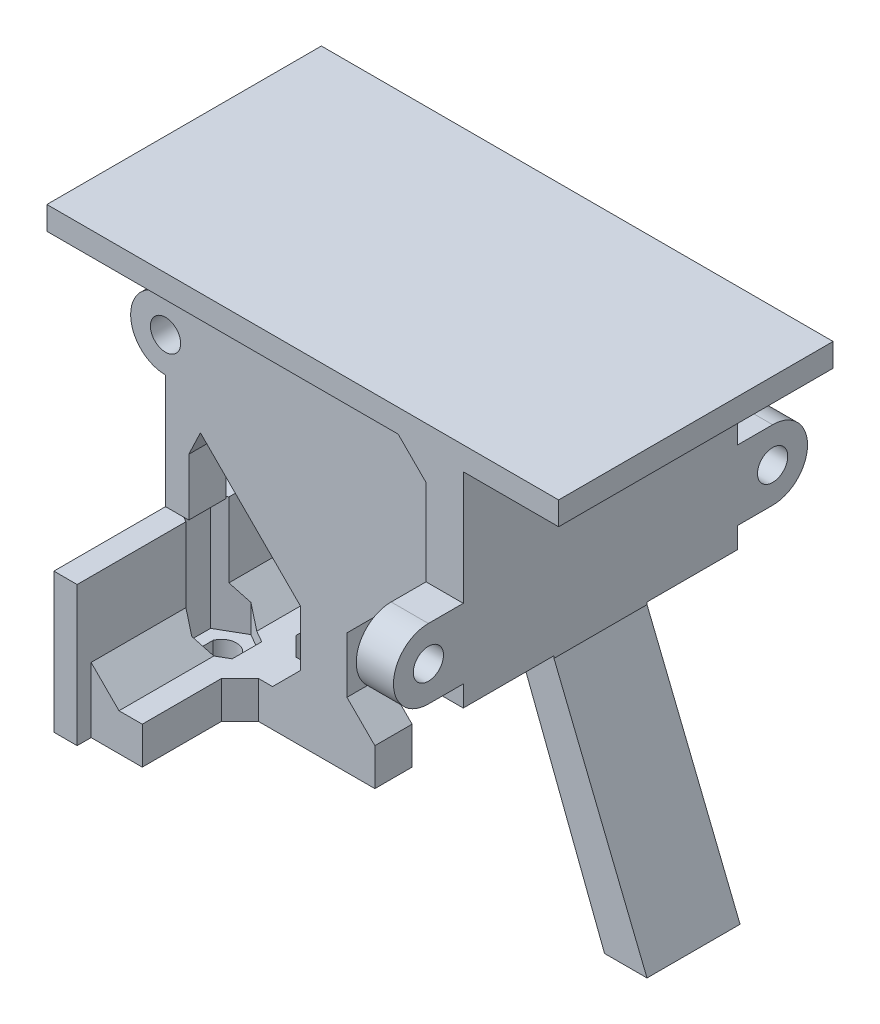
SolidWorks part; units mm, degrees
ref_plane "Alzado" through (0, 0, 0) normal (0, 0, 1) x (1, 0, 0)
ref_plane "Planta" through (0, 0, 0) normal (0, 1, 0) x (1, 0, 0)
ref_plane "Vista lateral" through (0, 0, 0) normal (1, 0, 0) x (0, 0, -1)
sketch "Croquis1" plane through (0, 0, 0) normal (0, 0, 1) x (1, 0, 0)
  line L0 (-14.75, 6) -> (-14.75, 3.75)
  line L1 (-14.75, 6) -> (14.75, 6)
  line L3 (-14.75, -6) -> (14.75, -6)
  line L5 (-14.75, 4.0227) -> (22, -6) construction
  line L6 (-22, -6) -> (22, 6) construction
  line L7 (-14.75, 3.75) -> (-18.5, 3.75)
  line L8 (-18.5, -3.75) -> (-14.75, -3.75)
  line L9 (-14.75, -3.75) -> (-14.75, -6)
  line L10 (14.75, -6) -> (14.75, -3.75)
  line L11 (14.75, -3.75) -> (18.5, -3.75)
  line L12 (14.75, 6) -> (14.75, 3.75)
  line L13 (14.75, 3.75) -> (18.5, 3.75)
  circle A0 centre (-18.5, 0) radius 1.625
  circle A1 centre (18.5, 0) radius 1.625
  arc A2 (-18.5, 3.75) -> (-18.5, -3.75) centre (-18.5, 0) ccw
  arc A3 (18.5, -3.75) -> (18.5, 3.75) centre (18.5, 0) ccw
  point P0 (0, 0)
  dimension "D1" = 3.25
  dimension "D6" = 7.5
  dimension "D7" = 7.5
  dimension "D2" = 37
  dimension "D3" = 18.5
  dimension "D5" = 12
extrude "Saliente-Extruir1" add sketch "Croquis1" along normal blind 4
sketch "Croquis2" plane through (0, 0, 4) normal (0, 0, 1) x (1, 0, 0)
  line L0 (-14.75, -6) -> (14.75, -6) construction
  line L1 (-4, -6) -> (1, -6)
  line L2 (-4, -6) -> (-4, -31)
  line L3 (-4, -31) -> (1, -31)
  line L4 (1, -6) -> (1, -31)
  dimension "D1" = 5
  dimension "D2" = 4
  dimension "D3" = 25
extrude "Saliente-Extruir2" add sketch "Croquis2" against normal blind 4
sketch "Croquis3" plane through (0, -31, 0) normal (0, -1, 0) x (1, 0, 0)
  line L0 (-10.5, -1.5) -> (-10.5, -10.5)
  line L5 (-18.5, 14.5) -> (-10.5, 14.5)
  line L6 (-18.5, 14.5) -> (-18.5, -10.5)
  line L7 (-22.25, 2) -> (-12.4182, 2) construction
  line L13 (-18.5, -10.5) -> (-10.5, -10.5)
  line L15 (-10.5, 14.5) -> (-10.5, 5.5)
  line L16 (-10.5, 5.5) -> (4, 5.5)
  line L19 (-10.5, -1.5) -> (4, -1.5)
  line L20 (4, 5.5) -> (4, -1.5)
  line L21 (-18.5, 4) -> (-18.5, 0) construction
  circle A4 centre (-14.5, 2) radius 1.625
  line M6 (1, 4) -> (-4, 4)
  line M7 (-4, 4) -> (-4, 0)
  line M8 (-4, 0) -> (1, 0)
  line M9 (1, 0) -> (1, 4)
  dimension "D3" = 25
  dimension "D9" = 7
  dimension "D5" = 3.25
  dimension "D10" = 4
  dimension "D1" = 8
  dimension "D2" = 12.5
  dimension "D8" = 3.5
  dimension "D6" = 12.5
extrude "Saliente-Extruir3" add sketch "Croquis3" against normal blind 4 contours M8 | M9 M6 M7 M8 | M7 M6 M9 region at (-11.2721, -31, 2) region at (-1.5, -31, 2)
chamfer "Chaflán1" distance 3 angle 45 1 edges at (-4, -27, 2)
chamfer "Chaflán2" distance 1.5 angle 45 2 edges at (-10.5, -29, -1.5) (-10.5, -29, 5.5)
sketch "Croquis4" plane through (0, 0, 4) normal (0, 0, 1) x (1, 0, 0)
  line L1 (18.5, -6) -> (26.25, -6)
  line L2 (18.5, -6) -> (18.5, 6)
  line L3 (18.5, 6) -> (26.25, 6)
  line L4 (26.25, -6) -> (26.25, 6)
  arc A0 (18.5, -3.75) -> (18.5, 3.75) centre (18.5, 0) ccw construction
  circle A1 centre (18.5, 0) radius 1.625 construction
  point P7 (22.25, 0)
  dimension "D1" = 4
  dimension "D2" = 0
extrude "Saliente-Extruir4" add sketch "Croquis4" along normal blind 21 and the other way blind 25
sketch "Croquis5" plane through (0, 6, 0) normal (0, 1, 0) x (1, 0, 0)
  line L0 (26.25, 21) -> (18.5, 21) construction
  line L1 (18.5, 0) -> (22.25, 0)
  line L2 (18.5, 0) -> (18.5, 21)
  line L3 (18.5, 21) -> (22.25, 21)
  line L4 (22.25, 0) -> (22.25, 21)
  line L6 (18.5, -4) -> (22.25, -4)
  line L7 (18.5, -4) -> (18.5, -25)
  line L8 (18.5, -25) -> (22.25, -25)
  line L9 (22.25, -4) -> (22.25, -25)
  line L10 (26.25, -25) -> (18.5, -25) construction
  line L11 (26.25, 21) -> (26.25, -25) construction
  line L12 (14.75, -4) -> (-14.75, -4) construction
  dimension "D1" = 4
  dimension "D2" = 4
extrude "Cortar-Extruir1" cut sketch "Croquis5" against normal through all both and the other way through all
sketch "Croquis6" plane through (0, 0, 4) normal (0, 0, 1) x (1, 0, 0)
  line L0 (18.5, -1.625) -> (18.5, 1.625) construction
  line L1 (18.5, 3.75) -> (22.25, 6)
  line L2 (22.25, 6) -> (18.5, 6)
  line L3 (18.5, 6) -> (18.5, 3.75)
  line L4 (18.5, -3.75) -> (22.25, -6)
  line L5 (22.25, -6) -> (18.5, -6)
  line L6 (18.5, -6) -> (18.5, -3.75)
  circle A0 centre (18.5, 0) radius 1.625
extrude "Cortar-Extruir2" cut sketch "Croquis6" against normal through all both and the other way through all
chamfer "Chaflán4" distance 5 angle 45 2 edges at (22.25, 0, 0) (22.25, 0, 4)
sketch "Croquis7" plane through (0, 0, 4) normal (0, 0, 1) x (1, 0, 0)
  circle A0 centre (18.5, 0) radius 3.745
  dimension "D1" = 7.49
extrude "Cortar-Extruir5" cut sketch "Croquis7" along normal blind 22
sketch "Croquis8" plane through (0, 0, 0) normal (0, 0, -1) x (-1, 0, 0)
  circle A0 centre (-18.5, 0) radius 3.745
extrude "Cortar-Extruir6" cut sketch "Croquis8" along normal blind 22
sketch "Croquis9" plane through (26.25, 0, 0) normal (1, 0, 0) x (0, 0, -1)
  line L1 (-16.75, 6) -> (-16.75, 3.75)
  line L2 (21, 6) -> (-25, 6) construction
  line L3 (-16.75, 3.75) -> (-20.5, 3.75)
  line L4 (-16.75, -6) -> (-16.75, -3.75)
  line L5 (21, -6) -> (-25, -6) construction
  line L6 (-16.75, -3.75) -> (-20.5, -3.75)
  line L7 (12.75, -6) -> (12.75, -3.75)
  line L8 (12.75, -3.75) -> (16.5, -3.75)
  line L9 (12.75, 6) -> (12.75, 3.75)
  line L10 (12.75, 3.75) -> (16.5, 3.75)
  line L11 (-16.75, 6) -> (-25, 6)
  line L12 (-25, 6) -> (-25, -6)
  line L13 (-25, -6) -> (-16.75, -6)
  line L14 (12.75, 6) -> (21, 6)
  line L15 (21, -6) -> (21, 6) construction
  line L16 (21, 6) -> (21, -6)
  line L17 (21, -6) -> (12.75, -6)
  line L18 (-2, 1.625) -> (-2, 19.0588) construction
  line L19 (0, 1.625) -> (-4, 1.625) construction
  arc A2 (-20.5, 3.75) -> (-20.5, -3.75) centre (-20.5, 0) ccw
  arc A3 (16.5, -3.75) -> (16.5, 3.75) centre (16.5, 0) ccw
  dimension "D1" = 37
  dimension "D2" = 18.5
  dimension "D4" = 7.5
extrude "Cortar-Extruir7" cut sketch "Croquis9" against normal blind 22
sketch "Croquis10" plane through (26.25, 0, 0) normal (1, 0, 0) x (0, 0, -1)
  line L0 (-2, -1.625) -> (-2, 16.9497) construction
  circle A0 centre (-20.5, 0) radius 1.625
  circle A1 centre (16.5, 0) radius 1.625
  arc A2 (-20.5, 3.75) -> (-20.5, -3.75) centre (-20.5, 0) ccw construction
  arc A3 (16.5, -3.75) -> (16.5, 3.75) centre (16.5, 0) ccw construction
  dimension "D1" = 3.25
  dimension "D2" = 3.25
extrude "Cortar-Extruir8" cut sketch "Croquis10" against normal blind 22
chamfer "Chaflán5" distance 12 angle 45 2 edges at (-4, -6, 2) (1, -6, 2)
sketch "Croquis11" plane through (0, -31, 0) normal (0, -1, 0) x (1, 0, 0)
  line L0 (4, 2) -> (-9.3695, 2) construction
  line L1 (-18.5, 16) -> (-16, 16)
  line L2 (-18.5, 16) -> (-18.5, -12)
  line L3 (-18.5, -12) -> (-16, -12)
  line L4 (-16, 16) -> (-16, -12)
  line L5 (-18.5, 14.5) -> (-18.5, -10.5) construction
  dimension "D1" = 28
  dimension "D2" = 14
  dimension "D3" = 2.5
extrude "Saliente-Extruir5" add sketch "Croquis11" against normal blind 15
chamfer "Chaflán6" distance 3 angle 45 2 edges at (-16, -27, -4.5625) (-16, -27, 8.5625)
sketch "Croquis12" plane through (0, -31, 0) normal (0, -1, 0) x (1, 0, 0)
  line L13 (-11.75, 0.4123) -> (-11.75, 3.5877)
  line L14 (-11.75, 3.5877) -> (-14.5, 5.1754)
  line L15 (-14.5, 5.1754) -> (-17.25, 3.5877)
  line L16 (-17.25, 3.5877) -> (-17.25, 0.4123)
  line L17 (-17.25, 0.4123) -> (-14.5, -1.1754)
  line L18 (-14.5, -1.1754) -> (-11.75, 0.4123)
  circle A0 centre (-14.5, 2) radius 2.75 construction
  dimension "D1" = 5.5
extrude "Cortar-Extruir9" cut sketch "Croquis12" against normal up to surface (15 mm away) from offset 2.5 up to face at (-17.25, -16, 2) offset against normal yes
sketch "Croquis13" plane through (0, -27, 0) normal (0, 1, 0) x (1, 0, 0)
  line L0 (-10.5, 3) -> (-10.5, 2)
  line L1 (-10.5, 2) -> (-8.5, 0)
  line L2 (14.75, 0) -> (-14.75, 0) construction
  line L3 (-8.5, 0) -> (4, 0)
  line L4 (4, 0) -> (4, 5.165)
  line L5 (4, 5.165) -> (-10.5, 3)
  line L6 (-18.5, -2) -> (0.9317, -2) construction
  line L7 (-18.5, -4) -> (-18.5, 0) construction
  line L8 (4, -9.165) -> (-10.5, -7)
  line L9 (4, -4) -> (4, -9.165)
  line L10 (-8.5, -4) -> (4, -4)
  line L11 (-10.5, -6) -> (-8.5, -4)
  line L12 (-10.5, -7) -> (-10.5, -6)
  dimension "D1" = 2
  dimension "D2" = 2
extrude "Cortar-Extruir10" cut sketch "Croquis13" against normal blind 10
sketch "Croquis14" plane through (26.25, 0, 0) normal (1, 0, 0) x (0, 0, -1)
  line L0 (2, -31) -> (10.5, -31) construction
  line L1 (-7, -6) -> (3, -6)
  line L2 (-7, -6) -> (-7, -31)
  line L3 (-7, -31) -> (3, -31)
  line L4 (3, -6) -> (3, -31)
  line L5 (-4, -27) -> (-4, -18) construction
  dimension "D1" = 10
  dimension "D2" = 3
  dimension "D3" = 25
extrude "Saliente-Extruir6" add sketch "Croquis14" against normal blind 8 and the other way blind 10
sketch "Croquis15" plane through (0, 6, 0) normal (0, 1, 0) x (1, 0, 0)
  line L0 (14.75, -4) -> (14.75, 0) construction
  line L1 (-14.75, -4) -> (14.75, -4)
  line L2 (-14.75, -4) -> (-14.75, 0)
  line L3 (-14.75, 0) -> (14.75, 0)
  line L4 (14.75, -4) -> (14.75, 0)
  line L6 (22.25, 12.75) -> (26.25, 12.75)
  line L7 (22.25, 12.75) -> (22.25, -16.75)
  line L8 (22.25, -16.75) -> (26.25, -16.75)
  line L9 (26.25, 12.75) -> (26.25, -16.75)
extrude "Saliente-Extruir7" add sketch "Croquis15" along normal blind 10
sketch "Croquis16" plane through (0, 16, 0) normal (0, 1, 0) x (1, 0, 0)
  line L1 (-18.5, 12.75) -> (36.5, 12.75)
  line L2 (-18.5, 12.75) -> (-18.5, -16.75)
  line L3 (-18.5, -16.75) -> (36.5, -16.75)
  line L4 (36.5, 12.75) -> (36.5, -16.75)
  line L6 (26.25, 12.75) -> (22.25, 12.75) construction
  line L7 (-18.5, -16) -> (-18.5, 12) construction
  dimension "D1" = 29.5
  dimension "D2" = 55
extrude "Saliente-Extruir8" add sketch "Croquis16" along normal blind 2.5
chamfer "Chaflán7" distance 3 angle 45 3 edges at (14.75, 16, 2) (-14.75, 16, 2) (22.25, 16, 2)
sketch "Croquis17" plane through (0, 0, 4) normal (0, 0, 1) x (1, 0, 0)
  line L0 (-18.5, -16) -> (-18.5, -3.75)
  line L1 (-18.5, -3.75) -> (-14.75, -3.75)
  line L2 (-14.75, -3.75) -> (-14.75, -7.25)
  line L3 (-14.75, -7.25) -> (-16, -9.875)
  line L4 (-16, -9.875) -> (-16, -16)
  line L5 (-16, -16) -> (-18.5, -16)
extrude "Saliente-Extruir9" add sketch "Croquis17" against normal up to surface (4 mm away) up to face at (0.9325, -7.3558, 0)
chamfer "Chaflán11" distance 3 1 edges at (1, -27, 2)
chamfer "Chaflán12" distance 25 angle 22 1 edges at (36.25, -6, 2) first distance on face at (36.25, -18.5, 2)
chamfer "Chaflán14" distance 35 angle 21 1 edges at (18.25, -31, 2) first distance on face at (18.25, -18.5, 2)
